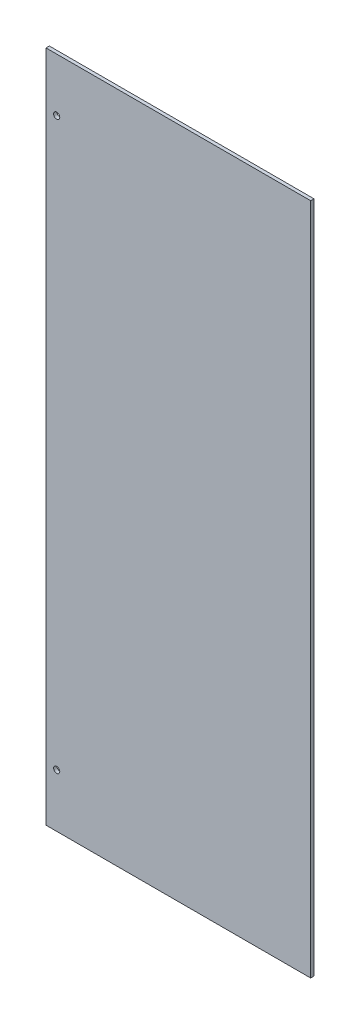
SolidWorks part; units mm, degrees
material "6061 Alloy"
ref_plane "Front" through (0, 0, 0) normal (0, 0, 1) x (1, 0, 0)
ref_plane "Top" through (0, 0, 0) normal (0, 1, 0) x (1, 0, 0)
ref_plane "Right" through (0, 0, 0) normal (1, 0, 0) x (0, 0, -1)
sketch "Sketch1" plane through (0, 0, 0) normal (0, 0, 1) x (1, 0, 0)
  line L1 (0, 0) -> (126.0475, 0)
  line L2 (0, 0) -> (0, 320.675)
  line L3 (0, 320.675) -> (126.0475, 320.675)
  line L4 (126.0475, 0) -> (126.0475, 320.675)
  dimension "D1" = 320.675
  dimension "D2" = 126.0475
extrude "Boss-Extrude1" add sketch "Sketch1" along normal blind 1.5875
sketch "Sketch2" plane through (0, 0, 1.5875) normal (0, 0, 1) x (1, 0, 0)
  line L0 (0, 320.675) -> (0, 0) construction
  line L1 (126.0475, 320.675) -> (0, 320.675) construction
  circle A0 centre (5.08, 295.275) radius 1.4605
  dimension "D3" = 2.921
  dimension "D1" = 5.08
  dimension "D2" = 25.4
extrude "Cut-Extrude1" cut sketch "Sketch2" against normal blind 6.35
pattern_linear "LPattern1" count 2 spacing 269.875 along (0, -1, 0) of "Cut-Extrude1"
